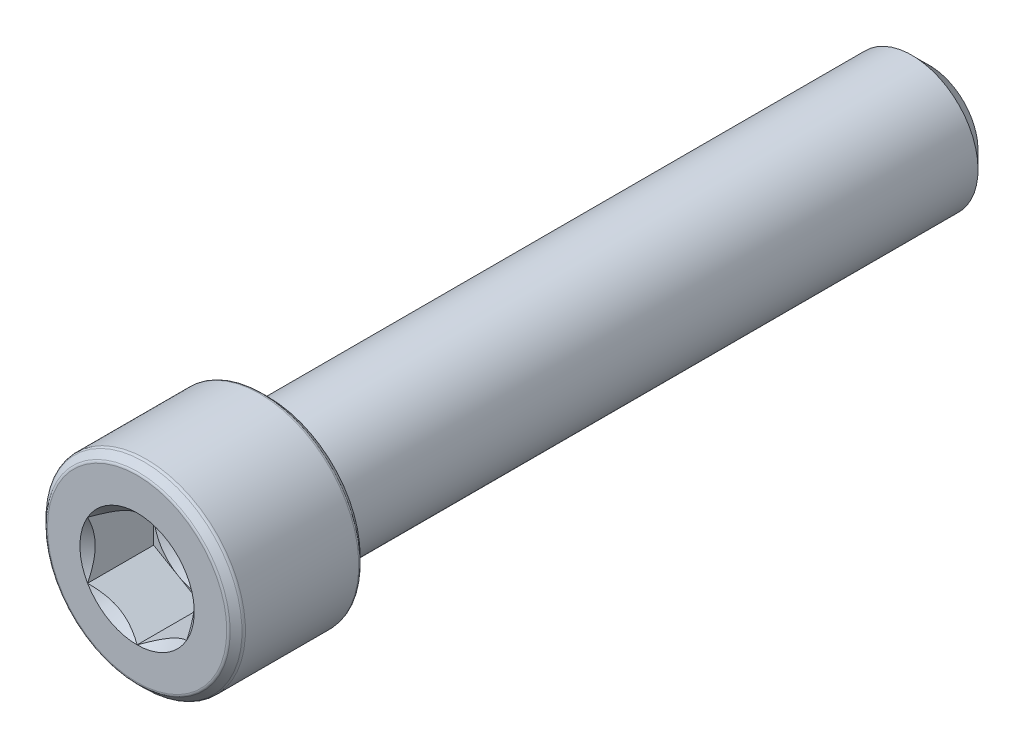
SolidWorks part; units mm, degrees
ref_plane "Front Plane" through (0, 0, 0) normal (0, 0, 1) x (1, 0, 0)
ref_plane "Top Plane" through (0, 0, 0) normal (0, 1, 0) x (1, 0, 0)
ref_plane "Right Plane" through (0, 0, 0) normal (1, 0, 0) x (0, 0, -1)
sketch "Sketch1" plane through (0, 0, 0) normal (1, 0, 0) x (0, 0, -1)
  line L0 (-19.05, 0) -> (19.05, 0) construction
  line L1 (-19.05, 0) -> (-19.05, 4.7625)
  line L2 (-19.05, 4.7625) -> (-12.7, 4.7625)
  line L3 (-12.7, 4.7625) -> (-12.7, 3.175)
  line L4 (-12.7, 3.175) -> (18.2251, 3.175)
  line L5 (18.9706, 3.3125) -> (19.6056, 2.2126) construction
  line L6 (19.6056, 2.2126) -> (20.2406, 3.3125) construction
  line L7 (20.2406, 3.3125) -> (18.9706, 3.3125) construction
  line L8 (18.2251, 3.175) -> (19.05, 2.3501)
  line L9 (19.05, 2.3501) -> (19.05, 0)
  line L10 (19.05, 3.175) -> (20.1612, 3.175) construction
  line L11 (19.6056, 3.3125) -> (19.6056, 3.175) construction
  line L12 (19.6056, 3.175) -> (19.6056, 2.3501) construction
  line L13 (19.6056, 2.3501) -> (19.6056, 2.2126) construction
  line L14 (19.5262, 2.3501) -> (19.685, 2.3501)
  line L15 (19.0103, 3.2437) -> (20.2009, 3.2437)
  line L16 (19.685, 2.3501) -> (20.2009, 3.2437)
  line L17 (19.5262, 2.3501) -> (19.0103, 3.2437)
  line L18 (-19.05, 2.3813) -> (-15.875, 2.3813)
  line L19 (-15.875, 2.3813) -> (-15.875, 0)
  line L20 (15.875, 3.175) -> (15.875, -3.175) construction
  point P20 (19.6056, 3.2437)
  point P22 (15.875, -3.175)
  point P28 (15.875, 0)
  point P29 (18.2251, -3.175)
  point P30 (-14.2875, 4.7625)
  dimension "Head Diameter" = 9.525
  dimension "Length" = 31.75
  dimension "Head Height" = 6.35
  dimension "Screw Size Decimal Equivalent" = 6.35
  dimension "D1" = 45
  dimension "Thread Pitch" = 1.27
  dimension "D3" = 0.1588
  dimension "Drive Size" = 4.7625
  dimension "D4" = 3.175
  dimension "D5" = 3.175
  dimension "D2" = 4.7625
sketch "Sketch3" plane through (0, 0, 0) normal (1, 0, 0) x (0, 0, -1)
  line L0 (-19.05, 4.3125) -> (-19.05, 2.3813)
  line L1 (-19.05, 2.3813) -> (-15.875, 2.3813)
  line L2 (-15.875, 2.3813) -> (-15.875, 0)
  line L3 (-15.875, 0) -> (19.05, 0)
  line L4 (19.05, 0) -> (19.05, 2.3501)
  line L5 (19.05, 2.3501) -> (18.2251, 3.175)
  line L6 (18.2251, 3.175) -> (-12.7, 3.175)
  line L7 (-12.7, 3.175) -> (-12.7, 4.3125)
  line L8 (-13.15, 4.7625) -> (-18.6, 4.7625)
  line L9 (-19.0012, 4.4303) -> (-18.7178, 4.7137)
  line L10 (-13.0322, 4.7137) -> (-12.7488, 4.4303)
  line L11 (-19.05, 4.7625) -> (-12.7, 4.7625) construction
  arc A0 (-18.7178, 4.7137) -> (-18.6, 4.7625) centre (-18.6, 4.5958) cw
  arc A1 (-19.0012, 4.4303) -> (-19.05, 4.3125) centre (-18.8833, 4.3125) ccw
  arc A2 (-12.7488, 4.4303) -> (-12.7, 4.3125) centre (-12.8667, 4.3125) cw
  arc A3 (-13.0322, 4.7137) -> (-13.15, 4.7625) centre (-13.15, 4.5958) ccw
  point P25 (-19.05, 4.3815)
  dimension "D3" = 0.1667
  dimension "D1" = 45
  dimension "D2" = 0.381
revolve "Revolve1" add sketch "Sketch3" angle 360 about L0
sketch "Sketch4" plane through (0, 0, 19.05) normal (0, 0, 1) x (1, 0, 0)
  line L1 (0, 2.7496) -> (-2.3812, 1.3748)
  line L2 (-2.3812, 1.3748) -> (-2.3812, -1.3748)
  line L3 (-2.3812, -1.3748) -> (0, -2.7496)
  line L4 (0, -2.7496) -> (2.3812, -1.3748)
  line L5 (2.3812, -1.3748) -> (2.3812, 1.3748)
  line L6 (2.3812, 1.3748) -> (0, 2.7496)
  circle A0 centre (0, 0) radius 2.3812 construction
extrude "Cut-Extrude1" cut sketch "Sketch4" against normal up to vertex (3.175 mm away) up to point (0, 2.3813, 15.875)
sketch "Sketch5" plane through (0, 0, 19.05) normal (0, 0, 1) x (1, 0, 0)
  circle A0 centre (0, 0) radius 2.7496
extrude "Cut-Extrude2" cut sketch "Sketch5" against normal up to next (3.175 mm away) draft 45
sketch "Sketch10" plane through (0, 0, 15.875) normal (0, 0, 1) x (1, 0, 0)
  line L0 (2.3812, 1.3748) -> (2.3812, -1.3748) construction
  circle A0 centre (0, 0) radius 2.3812
extrude "Cut-Extrude3" cut sketch "Sketch10" against normal through all draft 60
equation "\"D3@Sketch1\" = \"Thread Pitch@Sketch1\" / 8"
equation "\"D4@Sketch1\"=\"Thread Pitch@Sketch1\" * 2.5"
equation "\"D5@Sketch1\"=\"Head Height@Sketch1\"*0.5"
equation "\"D2@Sketch3\"=\"Head Diameter@Sketch1\" /25"
equation "\"D3@Sketch3\"=\"D2@Sketch3\"*0.4375"
equation "\"D2@Sketch1\"=\"Head Height@Sketch1\"*0.75"
equation "\"Pitch Natural Taper Angle\"= ATN ( \"Thread Pitch@Sketch1\" / 2 )"
equation "\"Angle Count\"= 60 / \"Pitch Natural Taper Angle\""
equation "\"Rounded Angle Count\"= ROUND ( \"Angle Count\" )"
equation "\"Taper Angle\"= \"Rounded Angle Count\" * \"Pitch Natural Taper Angle\""
